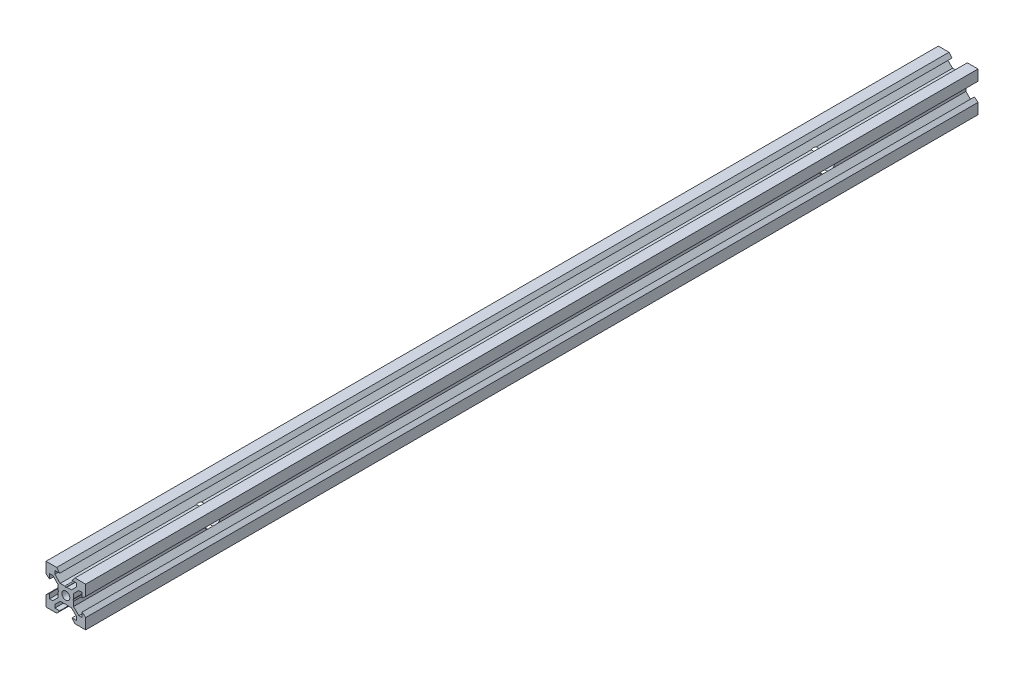
SolidWorks part; units mm, degrees
material "1060 Alloy"
ref_plane "Front Plane" through (0, 0, 0) normal (0, 0, 1) x (1, 0, 0)
ref_plane "Top Plane" through (0, 0, 0) normal (0, 1, 0) x (1, 0, 0)
ref_plane "Right Plane" through (0, 0, 0) normal (1, 0, 0) x (0, 0, -1)
sketch "Sketch1" plane through (0, 0, 0) normal (0, 0, 1) x (1, 0, 0)
  line L0 (10, 10) -> (4.6104, 10) construction
  line L1 (10, 10) -> (10, 4.6104) construction
  line L2 (10, -10) -> (10, -4.6104) construction
  line L3 (10, -10) -> (4.6104, -10) construction
  line L4 (10, 10) -> (10, 4.6104)
  line L5 (6.5607, 5.5) -> (8.2, 5.5)
  line L6 (5.5, 8.2) -> (5.5, 6.5607)
  line L7 (10, 10) -> (4.6104, 10)
  line L8 (10, 10) -> (10, 4.6104)
  line L9 (6.5607, 5.5) -> (3.9, 2.8393)
  line L10 (5.5, 6.5607) -> (2.8393, 3.9)
  line L11 (10, 4.6104) -> (8.2, 3.1)
  line L12 (4.6104, 10) -> (3.1, 8.2)
  line L13 (8.2, 3.1) -> (8.2, 5.5)
  line L14 (3.1, 8.2) -> (5.5, 8.2)
  line L15 (-6.5607, 5.5) -> (-8.2, 5.5)
  line L16 (6.5607, -5.5) -> (8.2, -5.5)
  line L17 (3.1, -8.2) -> (5.5, -8.2)
  line L18 (8.2, -3.1) -> (8.2, -5.5)
  line L19 (4.6104, -10) -> (3.1, -8.2)
  line L20 (10, -4.6104) -> (8.2, -3.1)
  line L21 (0.5196, -3.9) -> (0, -3.6)
  line L22 (0.5196, 3.9) -> (0, 3.6)
  line L23 (3.6, 0) -> (3.9, -0.5196)
  line L24 (3.9, 0.5196) -> (3.6, 0)
  line L25 (3.9, 0.5196) -> (3.9, 2.8393)
  line L26 (2.8393, 3.9) -> (0.5196, 3.9)
  line L27 (3.9, -2.8393) -> (3.9, -0.5196)
  line L28 (2.8393, -3.9) -> (0.5196, -3.9)
  line L29 (5.5, -6.5607) -> (2.8393, -3.9)
  line L30 (6.5607, -5.5) -> (3.9, -2.8393)
  line L31 (10, -10) -> (10, -4.6104)
  line L32 (10, -10) -> (4.6104, -10)
  line L33 (5.5, -8.2) -> (5.5, -6.5607)
  line L34 (-6.5607, -5.5) -> (-8.2, -5.5)
  line L35 (10, -10) -> (10, -4.6104)
  line L36 (0, 0) -> (0, 8.2) construction
  line L37 (-10, -10) -> (-4.6104, -10) construction
  line L38 (-10, -10) -> (-10, -4.6104) construction
  line L39 (-10, 10) -> (-10, 4.6104) construction
  line L40 (-10, 10) -> (-4.6104, 10) construction
  line L41 (-10, -10) -> (-10, -4.6104)
  line L43 (-5.5, -8.2) -> (-5.5, -6.5607)
  line L44 (-10, -10) -> (-4.6104, -10)
  line L45 (-10, -10) -> (-10, -4.6104)
  line L46 (-6.5607, -5.5) -> (-3.9, -2.8393)
  line L47 (-5.5, -6.5607) -> (-2.8393, -3.9)
  line L48 (-2.8393, -3.9) -> (-0.5196, -3.9)
  line L49 (-3.9, -2.8393) -> (-3.9, -0.5196)
  line L50 (-2.8393, 3.9) -> (-0.5196, 3.9)
  line L51 (-3.9, 0.5196) -> (-3.9, 2.8393)
  line L52 (-3.9, 0.5196) -> (-3.6, 0)
  line L53 (-3.6, 0) -> (-3.9, -0.5196)
  line L54 (-0.5196, 3.9) -> (0, 3.6)
  line L55 (-0.5196, -3.9) -> (0, -3.6)
  line L56 (-10, -4.6104) -> (-8.2, -3.1)
  line L57 (-4.6104, -10) -> (-3.1, -8.2)
  line L58 (-8.2, -3.1) -> (-8.2, -5.5)
  line L59 (-3.1, -8.2) -> (-5.5, -8.2)
  line L60 (-10, -10) -> (10, -10) construction
  line L61 (-10, -10) -> (-10, 10) construction
  line L62 (-3.1, 8.2) -> (-5.5, 8.2)
  line L63 (-8.2, 3.1) -> (-8.2, 5.5)
  line L64 (-4.6104, 10) -> (-3.1, 8.2)
  line L65 (-10, 4.6104) -> (-8.2, 3.1)
  line L66 (-5.5, 6.5607) -> (-2.8393, 3.9)
  line L67 (-6.5607, 5.5) -> (-3.9, 2.8393)
  line L68 (-10, 10) -> (-10, 4.6104)
  line L69 (-10, 10) -> (-4.6104, 10)
  line L70 (-5.5, 8.2) -> (-5.5, 6.5607)
  line L71 (-10, 10) -> (10, 10) construction
  line L72 (-10, 10) -> (-10, 4.6104)
  line L73 (10, -10) -> (10, 10) construction
  line L74 (-10, -10) -> (10, 10) construction
  line L75 (-10, 10) -> (10, -10) construction
  circle A0 centre (0, 0) radius 2
  dimension "D7" = 4
  dimension "D1" = 20
  dimension "D2" = 5.3896
  dimension "D3" = 4.5
  dimension "D4" = 50
  dimension "D5" = 1.8
  dimension "D6" = 1.5104
  dimension "D8" = 5.5
  dimension "D9" = 120
  dimension "D10" = 0.3
  dimension "D11" = 2.3197
  dimension "D12" = 7.8
  dimension "D13" = 7.8
  dimension "D14" = 1.5
  dimension "D15" = 2.6607
extrude "Boss-Extrude1" add sketch "Sketch1" along normal blind 450 contours L70 L62 L64 L69 L68 L65 L63 L15 L67 L51 L52 L53 L49 L46 L34 L58 L56 L41 L44 L57 L59 L43 L47 L48 L55 L21 L28 L29 L33 L17 L19 L32 L31 L20 L18 L16 L30 L27 L23 L24 L25 L9 L5 L13 L11 L4 L7 L12 L14 L6 L10 region at (9.7172, 7.3052, 0)
sketch "Sketch2" plane through (3.9, 0, 0) normal (1, 0, 0) x (0, 0, -1)
  line L0 (-450, -0.5196) -> (-380, -0.5196) construction
  line L1 (-450, -0.5196) -> (0, -0.5196) construction
  line L2 (-380, -0.5196) -> (-380, 0) construction
  line L3 (0, -0.5196) -> (-70, -0.5196) construction
  line L4 (-380, 0) -> (-70, 0) construction
  line L5 (-70, 0) -> (-70, -0.5196) construction
  circle A0 centre (-380, 0) radius 4.1
  circle A1 centre (-70, 0) radius 4.1
  dimension "D2" = 8.2
  dimension "D4" = 8.2
  dimension "D1" = 70
  dimension "D3" = 70
extrude "Cut-Extrude1" cut sketch "Sketch2" against normal through all
